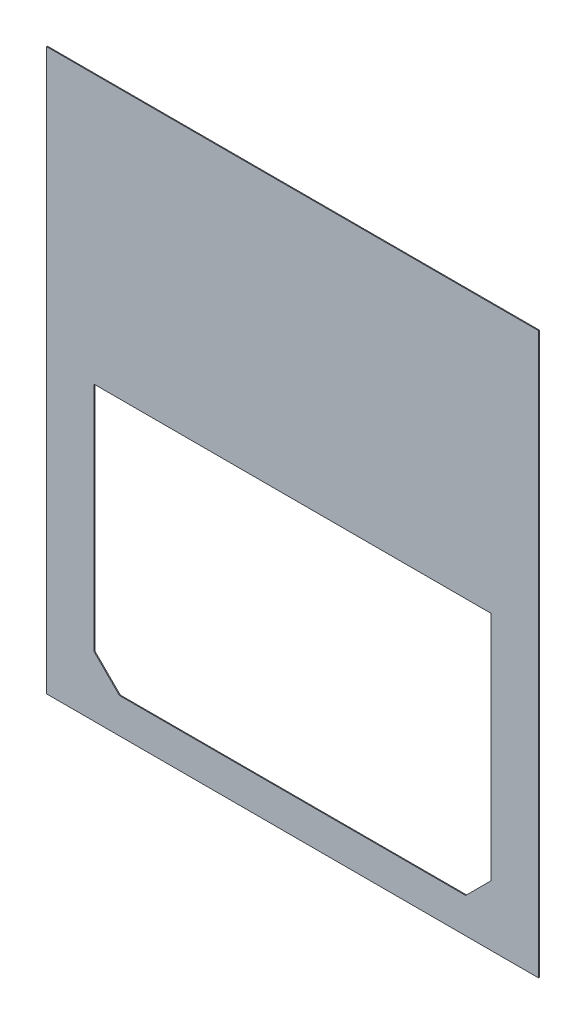
SolidWorks part; units mm, degrees
material "1.0037 (S235JR)"
ref_plane "Front Plane" through (0, 0, 0) normal (0, 0, 1) x (1, 0, 0)
ref_plane "Top Plane" through (0, 0, 0) normal (0, 1, 0) x (1, 0, 0)
ref_plane "Right Plane" through (0, 0, 0) normal (1, 0, 0) x (0, 0, -1)
sketch "Sketch1" plane through (0, 0, 0) normal (0, 0, 1) x (1, 0, 0)
  line L0 (-340, 500) -> (-340, 103.5)
  line L1 (-421.5, 0) -> (421.5, 0)
  line L2 (-421.5, 0) -> (-421.5, 960)
  line L3 (-421.5, 960) -> (421.5, 960)
  line L4 (421.5, 0) -> (421.5, 960)
  line L5 (-340, 103.5) -> (-296.5, 60)
  line L6 (-296.5, 60) -> (296.5, 60)
  line L7 (0, 960) -> (0, 0) construction
  line L8 (-340, 500) -> (340, 500)
  line L9 (340, 103.5) -> (296.5, 60)
  line L10 (340, 500) -> (340, 103.5)
  point P13 (0, 60)
  point P15 (0, 500)
  dimension "D1" = 843
  dimension "D2" = 45
  dimension "D3" = 680
  dimension "D4" = 60
  dimension "D5" = 440
  dimension "D6" = 960
  dimension "D7" = 125
base flange "Base-Flange1" sketch "Sketch1" thickness 1.5 reverse thickness direction no parameters "D1"=0.7366
sketch "Bend-Lines1" [suppressed] plane through (0, 0, 0) normal (0, 1, 0) x (1, 0, 0)
sketch "Bounding-Box1" [suppressed] plane through (0, 0, 0) normal (0, 1, 0) x (1, 0, 0)
sheet metal parameters "Sheet-Metal1" thickness 1.5 parameters "D1"=0.7366
flat pattern "Flat-Pattern1" [suppressed]
sketch "Bend-Lines2" plane through (0, 0, 0) normal (0, 1, 0) x (1, 0, 0)
sketch3d "Bounding-Box2" [suppressed]
  line L0 (421.5, 960, 0) -> (421.5, 0, 0) construction
  line L1 (-421.5, 960, 0) -> (-421.5, 0, 0) construction
  line L2 (421.5, 960, 0) -> (-421.5, 960, 0) construction
  line L3 (421.5, 0, 0) -> (-421.5, 0, 0) construction
